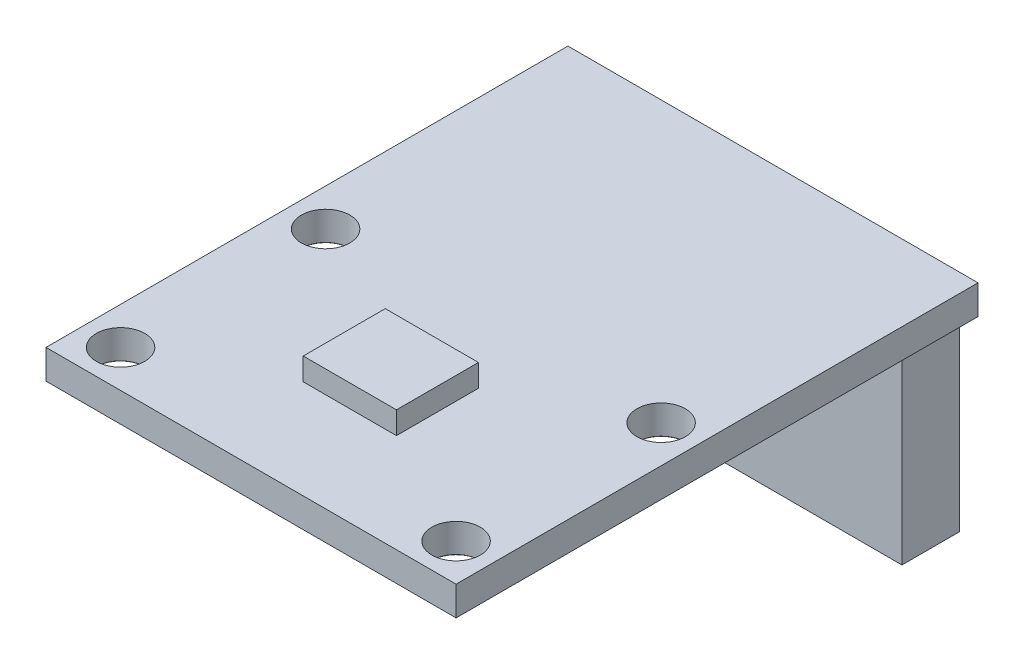
SolidWorks part; units mm, degrees
material "Massless"
ref_plane "Front Plane" through (0, 0, 0) normal (0, 0, 1) x (1, 0, 0)
ref_plane "Top Plane" through (0, 0, 0) normal (0, 1, 0) x (1, 0, 0)
ref_plane "Right Plane" through (0, 0, 0) normal (1, 0, 0) x (0, 0, -1)
ref_axis "X Axis" through (88.99, 0, 0) along (-1, 0, 0)
ref_axis "Y Axis" through (0, 55, 0) along (0, -1, 0)
ref_axis "Z Axis" through (0, 0, -88.99) along (0, 0, 1)
sketch "Sketch1" plane through (0, 0, 0) normal (0, 1, 0) x (1, 0, 0)
  line L1 (-11, 20.5) -> (11, 20.5)
  line L2 (-11, 20.5) -> (-11, -7.5)
  line L3 (-11, -7.5) -> (11, -7.5)
  line L4 (11, 20.5) -> (11, -7.5)
  line L5 (0, -7.5) -> (0, 20.5) construction
  line L6 (-11, 6.5) -> (11, 6.5) construction
  line L7 (9, -5.5) -> (-9, -5.5) construction
  line L8 (9, -5.5) -> (9, 5.5) construction
  line L9 (9, 5.5) -> (-9, 5.5) construction
  line L10 (-9, -5.5) -> (-9, 5.5) construction
  line L11 (0, 5.5) -> (0, -5.5) construction
  line L12 (9, 0) -> (-9, 0) construction
  line L13 (11, -7.5) -> (9, -7.5) construction
  line L14 (11, -7.5) -> (11, -5.5) construction
  line L15 (11, -5.5) -> (9, -5.5) construction
  line L16 (9, -7.5) -> (9, -5.5) construction
  point P0 (0, 6.5)
  point P4 (0, 0)
  dimension "D1" = 28
  dimension "D2" = 22
  dimension "D3" = 18
  dimension "D4" = 11
extrude "Boss-Extrude1" add sketch "Sketch1" along normal blind 1.57
sketch "Sketch4" plane through (0, 1.57, 0) normal (0, 1, 0) x (1, 0, 0)
  point P0 (-9, 5.5)
  point P3 (-9, -5.5)
  point P6 (9, -5.5)
  point P9 (9, 5.5)
hole_wizard "Ø2.6 (2.6) Diameter Hole1" positions "Sketch4" profile "Sketch3" hole size "Ø2.6" standard "ANSI Metric" end condition up to next
sketch "Sketch3" plane through (-9, 1.57, -5.5) normal (1, 0, 0) x (0, 0, 1)
  line L0 (0, 0) -> (0, 1.57)
  line L1 (0, 1.57) -> (1.325, 1.57)
  line L2 (1.3, 1.545) -> (1.3, 0)
  line L5 (1.3, 0) -> (0, 0)
  line L7 (1.325, 1.57) -> (1.3, 1.545)
  line L8 (-1.325, 1.57) -> (-1.3, 1.545) construction
  line L11 (0, -6.35) -> (0, 107.95) construction
  dimension "Thru Hole Dia." = 2.6
  dimension "Thru Hole Depth" = 1.57
  dimension "Far C'Sink Dia." = 2.65
  dimension "Far C'Sink Angle" = 90
sketch "Sketch5" plane through (0, 1.57, 0) normal (0, 1, 0) x (1, 0, 0)
  line L1 (-2.5, -2.2) -> (2.5, -2.2)
  line L2 (-2.5, -2.2) -> (-2.5, 2.2)
  line L3 (-2.5, 2.2) -> (2.5, 2.2)
  line L4 (2.5, -2.2) -> (2.5, 2.2)
  line L5 (0, 2.2) -> (0, -2.2) construction
  line L6 (-2.5, 0) -> (2.5, 0) construction
  point P0 (0, 0)
  dimension "D1" = 5
  dimension "D2" = 4.4
extrude "Boss-Extrude2" add sketch "Sketch5" along normal blind 1.2
sketch "Sketch6" plane through (0, 0, 0) normal (0, 1, 0) x (1, 0, 0)
  line L0 (11, 20.5) -> (11, -7.5) construction
  line L1 (-11, 20.5) -> (11, 20.5) construction
  line L2 (-11, 20.5) -> (-11, 16.42) construction
  line L3 (-11, 16.42) -> (11, 16.42) construction
  line L4 (11, 20.5) -> (11, 16.42) construction
  line L5 (-10.5, 20) -> (10.5, 20)
  line L6 (10.5, 20) -> (10.5, 16.92)
  line L7 (-10.5, 16.92) -> (10.5, 16.92)
  line L8 (-10.5, 20) -> (-10.5, 16.92)
  dimension "D1" = 4.08
  dimension "D2" = 0.5
extrude "Boss-Extrude3" add sketch "Sketch6" against normal blind 10
